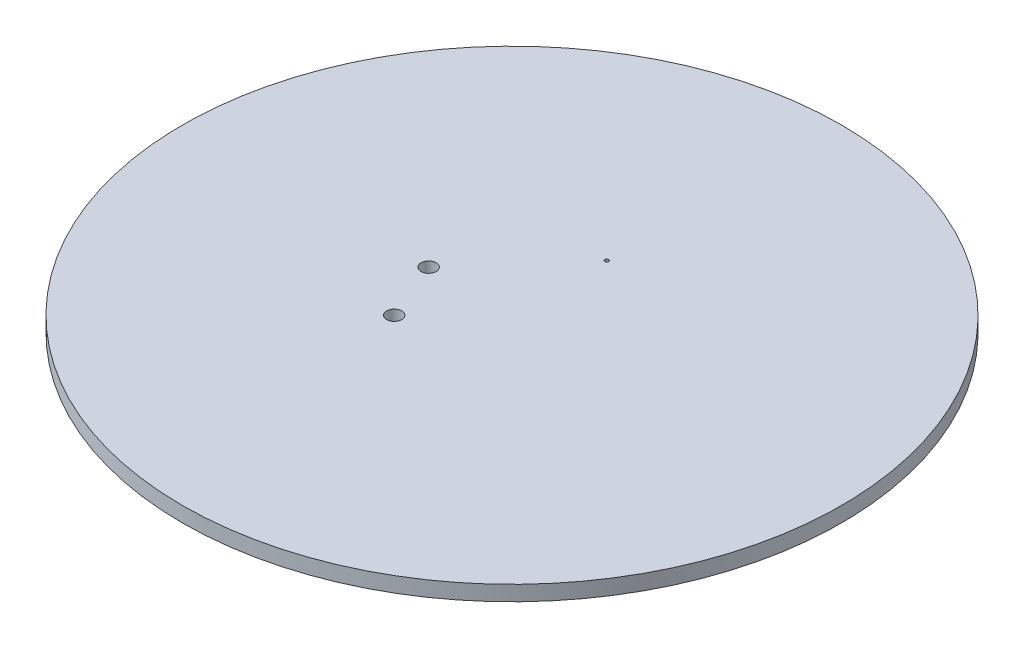
SolidWorks part; units mm, degrees
material "PTFE (general)"
ref_plane "Front Plane" through (0, 0, 0) normal (0, 0, 1) x (1, 0, 0)
ref_plane "Top Plane" through (0, 0, 0) normal (0, 1, 0) x (1, 0, 0)
ref_plane "Right Plane" through (0, 0, 0) normal (1, 0, 0) x (0, 0, -1)
sketch "Sketch1" plane through (0, 0, 0) normal (0, 1, 0) x (1, 0, 0)
  circle A0 centre (0, 0) radius 43.5
  dimension "D2" = 87
extrude "Boss-Extrude1" add sketch "Sketch1" along normal blind 2
sketch "Sketch2" plane through (0, 2, 0) normal (0, 1, 0) x (1, 0, 0)
  circle A0 centre (0, 12.5) radius 0.25
  dimension "D1" = 0.5
  dimension "D2" = 12.5
extrude "Cut-Extrude1" cut sketch "Sketch2" against normal through all both and the other way through all
sketch "Sketch3" plane through (0, 2, 0) normal (0, 1, 0) x (1, 0, 0)
  line L0 (0, 0) -> (-36.0536, 0) construction
  line L1 (0, 0) -> (0, 12.5) construction
  line L2 (0, 12.5) -> (0, 0) construction
  line L3 (0, 0) -> (-21.4265, -21.4265) construction
  circle A0 centre (-11, 0) radius 1
  circle A1 centre (-7.7782, -7.7782) radius 1
  dimension "D1" = 2
  dimension "D3" = 2
  dimension "D2" = 11
  dimension "D4" = 11
extrude "Cut-Extrude2" cut sketch "Sketch3" against normal through all both and the other way through all
